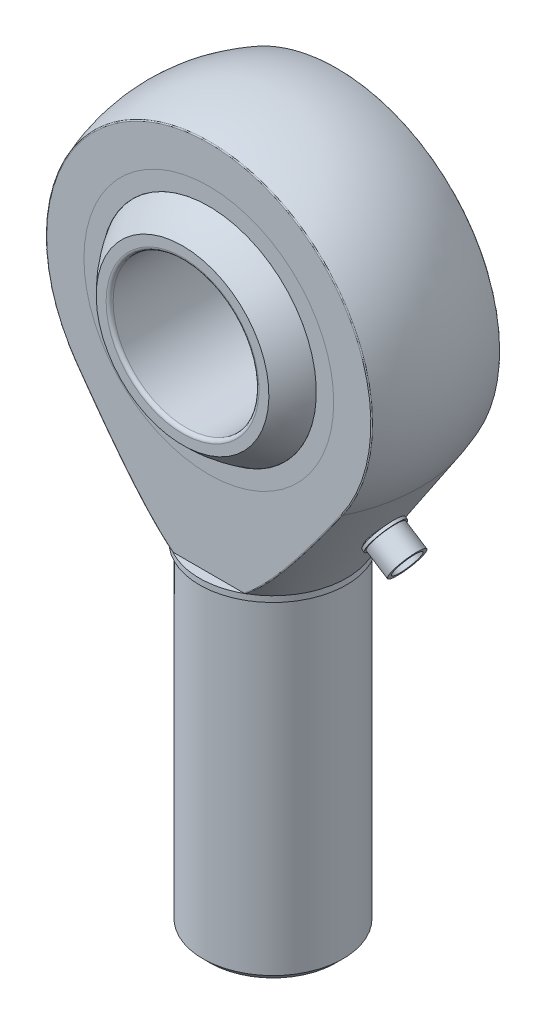
SolidWorks part; units mm, degrees
ref_plane "前视基准面" through (0, 0, 0) normal (0, 0, 1) x (1, 0, 0)
ref_plane "上视基准面" through (0, 0, 0) normal (0, 1, 0) x (1, 0, 0)
ref_plane "右视基准面" through (0, 0, 0) normal (1, 0, 0) x (0, 0, -1)
sketch "草图1" plane through (0, 0, 0) normal (1, 0, 0) x (0, 0, -1)
  line L0 (-64.7744, 0) -> (61.2295, 0) construction
  line L1 (0, 90.5552) -> (0, 0) construction
  line L2 (-12, 0) -> (-12, 57)
  line L3 (-25.0099, 94) -> (25.9127, 94) construction
  line L4 (-11, 64) -> (11, 64)
  line L5 (-11, 64) -> (-11, 124)
  line L6 (-11, 124) -> (11, 124)
  line L7 (11, 64) -> (11, 124)
  line L8 (-15.5, 108.7985) -> (-15.5, 106.5)
  line L9 (15.5, 108.7985) -> (15.5, 106.5)
  line L10 (-15.5, 106.5) -> (15.5, 106.5)
  line L11 (-15.5, 81.5) -> (15.5, 81.5)
  line L12 (-15.5, 81.5) -> (-15.5, 79.2015)
  line L13 (15.5, 81.5) -> (15.5, 79.2015)
  line L14 (-12, 57) -> (0, 57)
  line L15 (-12, 57) -> (-12.6, 57)
  line L16 (-12.6, 57) -> (-12.6, 58)
  line L17 (-12.6, 58) -> (0, 58)
  line L18 (-12.6, 58) -> (-11, 64)
  arc A0 (-15.5, 79.2015) -> (15.5, 79.2015) centre (0, 94) ccw
  arc A1 (15.5, 108.7985) -> (-15.5, 108.7985) centre (0, 94) ccw
  arc A2 (14.9, 106.5) -> (15.5, 107.1) centre (14.9, 107.1) ccw
  point P15 (0, 115.43)
  dimension "r1s" = 0.6
  dimension "D1" = 1
  dimension "h" = 94
  dimension "d2" = 60
  dimension "C1" = 22
  dimension "d" = 25
  dimension "dk" = 42.86
  dimension "B" = 31
  dimension "G" = 24
  dimension "L1" = 57
  dimension "D3" = 25.2
sketch "草图2" plane through (0, 0, 0) normal (0, 0, 1) x (1, 0, 0)
  line L0 (-31.4612, 0) -> (36.7298, 0) construction
  line L1 (0, 90.5552) -> (0, 0) construction
  line L2 (0, 90.5552) -> (0, 0) construction
  line L3 (-12, 57) -> (-12.6, 57)
  line L4 (-12.6, 57) -> (-12.6, 58)
  line L5 (0, 124) -> (0, 0)
  line L6 (-12.6, 58) -> (-25.2809, 77.8483)
  line L7 (-12, 57) -> (-12, 0)
  line L8 (-12, 0) -> (0, 0)
  arc A0 (0, 124) -> (-25.2809, 77.8483) centre (0, 94) ccw
  circle A1 centre (0, 94) radius 12.5
  dimension "D1" = 25.2
  dimension "D2" = 24
sketch "草图3" plane through (0, 0, 0) normal (0, 0, 1) x (1, 0, 0)
  line L0 (-12, 57) -> (-12.6, 57) construction
  line L1 (-12.6, 57) -> (-12.6, 58) construction
  line L2 (-12.6, 58) -> (-25.2809, 77.8483) construction
  line L3 (0, 124) -> (0, 0) construction
  line L4 (-12, 0) -> (0, 0) construction
  line L5 (-12, 57) -> (-12, 0) construction
  line L6 (-12, 57) -> (-12.6, 57)
  line L7 (-12.6, 57) -> (-12.6, 58)
  line L8 (-12.6, 58) -> (-25.2809, 77.8483)
  line L9 (0, 124) -> (0, 0)
  line L10 (-10.8, 0) -> (0, 0)
  line L11 (-12, 57) -> (-12, 1.2)
  line L12 (-10.8, 0) -> (-12, 1.2)
  arc A1 (0, 124) -> (-25.2809, 77.8483) centre (0, 94) ccw construction
  arc A3 (0, 124) -> (-25.2809, 77.8483) centre (0, 94) ccw
  dimension "D1" = 135
  dimension "D2" = 1.2
revolve "旋转2" add sketch "草图3" angle 360 about L9
cosmetic thread "装饰螺纹线1" parameters "D2"=20.64
sketch "草图4" plane through (0, 0, 0) normal (1, 0, 0) x (0, 0, -1)
  line L0 (-12.6, 58) -> (0, 58) construction
  line L1 (-11, 124) -> (-30, 124)
  line L2 (-11, 124) -> (-11, 58)
  line L3 (-11, 58) -> (-30, 58)
  line L4 (-30, 124) -> (-30, 58)
  line L5 (11, 124) -> (30, 124)
  line L6 (11, 124) -> (11, 58)
  line L7 (11, 58) -> (30, 58)
  line L8 (30, 124) -> (30, 58)
  arc A0 (25.2809, 77.8483) -> (-25.2809, 77.8483) centre (0, 94) ccw construction
extrude "切除-拉伸1" cut sketch "草图4" against normal through all and the other way through all
sketch "草图5" plane through (0, 0, 0) normal (1, 0, 0) x (0, 0, -1)
  line L0 (-15.5, 108.7985) -> (-15.5, 106.5) construction
  line L1 (-15.5, 106.5) -> (15.5, 106.5) construction
  line L2 (15.5, 108.7985) -> (15.5, 106.5) construction
  line L3 (-15.5, 81.5) -> (15.5, 81.5) construction
  line L4 (15.5, 81.5) -> (15.5, 79.2015) construction
  line L5 (-15.5, 81.5) -> (-15.5, 79.2015) construction
  line L6 (-15.5, 108.7985) -> (-15.5, 94)
  line L7 (-15.5, 106.5) -> (15.5, 106.5)
  line L8 (15.5, 108.7985) -> (15.5, 94)
  line L9 (-15.5, 81.5) -> (15.5, 81.5)
  line L10 (15.5, 81.5) -> (15.5, 79.2015)
  line L11 (-15.5, 81.5) -> (-15.5, 79.2015)
  line L12 (-11, 115.4013) -> (-1.1144, 117.1444)
  line L13 (-11, 64) -> (-11, 124) construction
  line L14 (-1.1144, 117.1444) -> (-1.1144, 115.401)
  line L15 (0, 90.5552) -> (0, 0) construction
  line L16 (0, 90.5552) -> (0, 0) construction
  line L17 (-11, 115.4013) -> (-11, 112.3914)
  line L18 (11, 115.4013) -> (11, 112.3914)
  line L19 (1.1144, 117.1444) -> (1.1144, 115.401)
  line L20 (11, 115.4013) -> (1.1144, 117.1444)
  line L21 (-1.1144, 117.1444) -> (1.1144, 117.1444) construction
  line L22 (-25.0099, 94) -> (25.9127, 94) construction
  line L23 (-25.0099, 94) -> (25.9127, 94) construction
  line L24 (-15.5, 94) -> (15.5, 94)
  arc A0 (15.5, 108.7985) -> (-15.5, 108.7985) centre (0, 94) ccw construction
  arc A1 (-15.5, 79.2015) -> (15.5, 79.2015) centre (0, 94) ccw construction
  arc A2 (15.5, 108.7985) -> (-15.5, 108.7985) centre (0, 94) ccw
  arc A3 (-15.5, 79.2015) -> (15.5, 79.2015) centre (0, 94) ccw
  dimension "D1" = 1.7144
  dimension "D2" = 2.2287
  dimension "D3" = 80
revolve "切除-旋转1" cut sketch "草图5" angle 360 about L3 region at (0, 110.2062, 0) region at (0, 100.25, 0) region at (0, 115.171, 6.5796) region at (0, 115.171, -6.5796)
revolve "旋转3" add sketch "草图5<4>" angle 360 about L3 region at (0, 115.171, 6.5796) region at (0, 115.171, -6.5796)
sketch "草图5<4>" plane through (0, 0, 0) normal (1, 0, 0) x (0, 0, -1) same geometry as "草图5"
fillet "圆角1" radius 0.02 1 edges at (18.3914, 94, 11)
fillet "圆角2" radius 0.02 2 edges at (21.4013, 94, -11) (18.3914, 94, -11)
revolve "旋转4" add sketch "草图5<5>" angle 360 about L3 region at (0, 110.2062, 0)
sketch "草图5<5>" plane through (0, 0, 0) normal (1, 0, 0) x (0, 0, -1) same geometry as "草图5"
fillet "圆角3" radius 0.2 6 edges at (0, 121.9106, -11) (0, 121.9106, 11)
fillet "圆角4" radius 0.6 2 edges at (12.5, 94, -15.5) (12.5, 94, 15.5)
sketch "草图6" plane through (0, 0, 0) normal (0, 0, 1) x (1, 0, 0)
  line L0 (18.9404, 67.9242) -> (36.774, 56.5305) construction
  line L1 (0, 90.5552) -> (0, 0) construction
  line L2 (0, 90.5552) -> (0, 0) construction
  line L3 (-12.6, 58) -> (-25.2809, 77.8483) construction
  line L4 (-12.6, 58) -> (-25.2809, 77.8483) construction
  line L5 (12.6, 58) -> (25.2809, 77.8483) construction
  line L6 (19.7213, 70.9852) -> (20.564, 70.4469)
  line L7 (20.564, 70.4469) -> (20.7256, 70.6997)
  line L8 (20.7256, 70.6997) -> (21.13, 70.4412)
  line L9 (21.13, 70.4412) -> (20.9685, 70.1884)
  line L10 (20.9685, 70.1884) -> (24.609, 67.8626)
  line L11 (24.609, 67.8626) -> (22.9938, 65.3345)
  line L12 (22.9938, 65.3345) -> (18.1062, 68.4572)
  line L13 (18.1062, 68.4572) -> (19.7213, 70.9852)
  line L14 (19.3983, 70.4796) -> (24.2859, 67.357)
  dimension "D1" = 0.01
  dimension "D2" = 6
  dimension "D3" = 4.8
  dimension "D4" = 6.6
  dimension "D5" = 4.8
  dimension "D6" = 0.48
  dimension "D7" = 1
revolve "旋转5" add sketch "草图6" angle 360 about L0 region at (21.9577, 69.2217, 0)
split "分割1" trim tools "右视基准面" bodies to split 108 resulting bodies 109 110
combine bodies "组合1" operation type add bodies to combine 110 109
